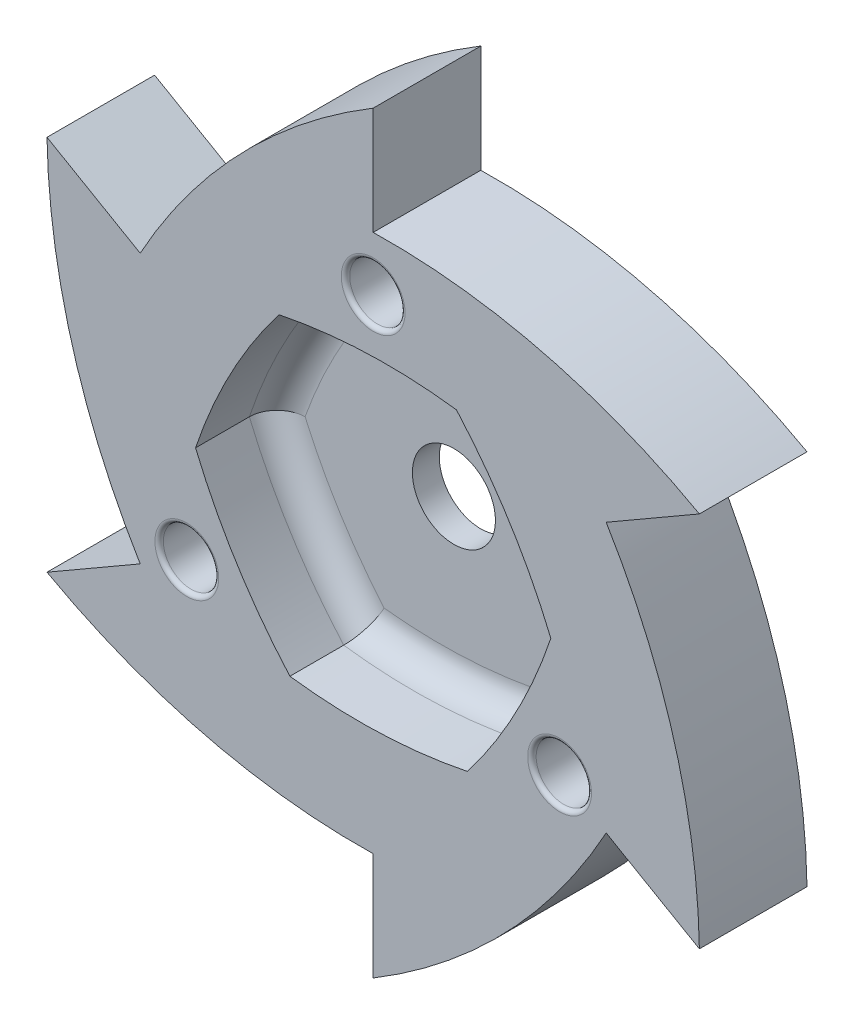
SolidWorks part; units mm, degrees
ref_plane "Front Plane" through (0, 0, 0) normal (0, 0, 1) x (1, 0, 0)
ref_plane "Top Plane" through (0, 0, 0) normal (0, 1, 0) x (1, 0, 0)
ref_plane "Right Plane" through (0, 0, 0) normal (1, 0, 0) x (0, 0, -1)
sketch "Sketch1" plane through (0, 0, 0) normal (0, 0, 1) x (1, 0, 0)
  line L0 (0, 0) -> (0, 31.75) construction
  line L1 (27.4963, 15.875) -> (38.4948, 22.225)
  line L2 (27.4963, -15.875) -> (38.4948, -22.225)
  line L3 (0, -31.75) -> (0, -44.45)
  line L4 (-27.4963, -15.875) -> (-38.4948, -22.225)
  line L5 (-27.4963, 15.875) -> (-38.4948, 22.225)
  line L6 (0, 31.75) -> (0, 44.45)
  line L7 (-20.9623, -0.7492) -> (-20.9623, -0.7492)
  line L8 (-9.8323, -18.5285) -> (-9.8323, -18.5285)
  line L9 (11.13, -17.7793) -> (11.13, -17.7793)
  line L10 (20.9623, 0.7492) -> (20.9623, 0.7492)
  line L11 (9.8323, 18.5285) -> (9.8323, 18.5285)
  line L12 (-11.13, 17.7793) -> (-11.13, 17.7793)
  line L13 (27.4963, 15.875) -> (24.4114, 20.9701) construction
  arc A0 (-11.13, 17.7793) -> (-20.9623, -0.7492) centre (39.2347, -20.8203) ccw
  arc A1 (38.4948, -22.225) -> (27.4963, 15.875) centre (-37.6483, -23.5681) ccw
  arc A2 (38.4948, 22.225) -> (0, 31.75) centre (1.5864, -44.3884) ccw
  arc A3 (0, -44.45) -> (27.4963, -15.875) centre (-39.2347, 20.8203) ccw
  arc A4 (-38.4948, -22.225) -> (0, -31.75) centre (-1.5864, 44.3884) ccw
  arc A5 (-38.4948, 22.225) -> (-27.4963, -15.875) centre (37.6483, 23.5681) ccw
  arc A6 (0, 44.45) -> (-27.4963, 15.875) centre (39.2347, -20.8203) ccw
  arc A7 (-20.9623, -0.7492) -> (-9.8323, -18.5285) centre (37.6483, 23.5681) ccw
  arc A8 (-9.8323, -18.5285) -> (11.13, -17.7793) centre (-1.5864, 44.3884) ccw
  arc A9 (11.13, -17.7793) -> (20.9623, 0.7492) centre (-39.2347, 20.8203) ccw
  arc A10 (20.9623, 0.7492) -> (9.8323, 18.5285) centre (-37.6483, -23.5681) ccw
  arc A11 (9.8323, 18.5285) -> (-11.13, 17.7793) centre (1.5864, -44.3884) ccw
  point P3 (0, 0)
  point P7 (42.5077, 12.9959)
  point P32 (0, 0)
  dimension "D1" = 6
  dimension "D2" = 12.7
  dimension "D3" = 60
extrude "Boss-Extrude1" add sketch "Sketch1" along normal blind 6.35 and the other way blind 6.35
sketch "Sketch3" plane through (0, 0, 6.35) normal (0, 0, 1) x (1, 0, 0)
  arc A0 (-11.13, 17.7793) -> (-20.9623, -0.7492) centre (39.2347, -20.8203) ccw construction
  arc A1 (9.8323, 18.5285) -> (-11.13, 17.7793) centre (1.5864, -44.3884) ccw construction
  arc A2 (20.9623, 0.7492) -> (9.8323, 18.5285) centre (-37.6483, -23.5681) ccw construction
  arc A3 (11.13, -17.7793) -> (20.9623, 0.7492) centre (-39.2347, 20.8203) ccw construction
  arc A4 (-9.8323, -18.5285) -> (11.13, -17.7793) centre (-1.5864, 44.3884) ccw construction
  arc A5 (-20.9623, -0.7492) -> (-9.8323, -18.5285) centre (37.6483, 23.5681) ccw construction
  arc A6 (-11.13, 17.7793) -> (-20.9623, -0.7492) centre (39.2347, -20.8203) ccw
  arc A7 (9.8323, 18.5285) -> (-11.13, 17.7793) centre (1.5864, -44.3884) ccw
  arc A8 (20.9623, 0.7492) -> (9.8323, 18.5285) centre (-37.6483, -23.5681) ccw
  arc A9 (11.13, -17.7793) -> (20.9623, 0.7492) centre (-39.2347, 20.8203) ccw
  arc A10 (-9.8323, -18.5285) -> (11.13, -17.7793) centre (-1.5864, 44.3884) ccw
  arc A11 (-20.9623, -0.7492) -> (-9.8323, -18.5285) centre (37.6483, 23.5681) ccw
extrude "Boss-Extrude2" add sketch "Sketch3" against normal blind 12.7
extrude "Cut-Extrude1" cut sketch "Sketch3<2>" against normal blind 9.525
sketch "Sketch3<2>" plane through (0, 0, 6.35) normal (0, 0, 1) x (1, 0, 0) same geometry as "Sketch3"
sketch "Sketch4" plane through (0, 0, 0) normal (1, 0, 0) x (0, 0, -1)
  line L0 (0, 44.45) -> (0, -44.45) construction
  line L1 (6.35, 44.45) -> (-6.35, 44.45) construction
  line L2 (6.35, -44.45) -> (-6.35, -44.45) construction
ref_plane "Plane1" through (0, 0, 0) normal (0, 0, 1) x (1, 0, 0)
fillet "Fillet1" radius 3.175 6 edges at (-16.137, -10.1019, -3.175) (0.68, -19.026, -3.175) (16.817, -8.9241, -3.175) (16.137, 10.1019, -3.175) (-0.68, 19.026, -3.175) (-16.817, 8.9241, -3.175)
hole_wizard "W (0.386) Diameter Hole1" positions "Sketch6" profile "Sketch5" hole size "W" standard "ANSI Inch" end condition through all
sketch "Sketch6" plane through (0, 0, -3.175) normal (0, 0, 1) x (1, 0, 0)
  point P0 (0, 0)
sketch "Sketch5" plane through (0, 0, -3.175) normal (1, 0, 0) x (0, -1, 0)
  line L0 (0, 0) -> (0, 3.175)
  line L1 (0, 3.175) -> (4.9022, 3.175)
  line L2 (4.9022, 3.175) -> (4.9022, 0)
  line L5 (4.9022, 0) -> (0, 0)
  line L11 (0, -6.35) -> (0, 107.95) construction
  dimension "Thru Hole Dia." = 9.8044
  dimension "Thru Hole Depth" = 3.175
hole_wizard "9/64 (0.14063) Diameter Hole1" positions "Sketch8" profile "Sketch7" hole size "9/64" standard "ANSI Inch" end condition through all
sketch "Sketch8" plane through (0, 0, -6.35) normal (0, 0, -1) x (-1, 0, 0)
  line L0 (0, 44.45) -> (0, -44.45) construction
  point P0 (0, 25.4)
  dimension "D1" = 25.4
sketch "Sketch7" plane through (0, 25.4, -6.35) normal (1, 0, 0) x (0, 1, 0)
  line L0 (0, 0) -> (0, 12.7)
  line L1 (0, 12.7) -> (1.786, 12.7)
  line L2 (1.786, 12.7) -> (1.786, 0)
  line L5 (1.786, 0) -> (0, 0)
  line L11 (0, -6.35) -> (0, 107.95) construction
  dimension "Thru Hole Dia." = 3.572
  dimension "Thru Hole Depth" = 12.7
pattern_circular "CirPattern1" count 3 every 120 about axis through (0, 0, -3.175) along (0, 0, 1) of "9/64 (0.14063) Diameter Hole1"
hole_wizard "F (0.257) Diameter Hole1" positions "Sketch10" profile "Sketch9" hole size "F" standard "ANSI Inch"
sketch "Sketch10" plane through (0, 0, 6.35) normal (0, 0, 1) x (1, 0, 0)
  point P0 (0, 25.4)
  point P3 (21.997, -12.7)
  point P6 (-21.997, -12.7)
sketch "Sketch9" plane through (0, 25.4, 6.35) normal (1, 0, 0) x (0, -1, 0)
  line L0 (0, 0) -> (0, 9.652)
  line L1 (0, 9.652) -> (3.2639, 9.652)
  line L2 (3.2639, 9.652) -> (3.2639, 0)
  line L5 (3.2639, 0) -> (0, 0)
  line L10 (0, 9.652) -> (-3.2639, 9.652) construction
  line L11 (0, -6.35) -> (0, 107.95) construction
  dimension "Hole Dia." = 6.5278
  dimension "Hole Depth" = 9.652
  dimension "Drill Angle" = 180
fillet "Fillet2" radius 0.5 3 edges at (25.2609, -12.7, 6.35) (3.2639, 25.4, 6.35) (-18.7331, -12.7, 6.35)
